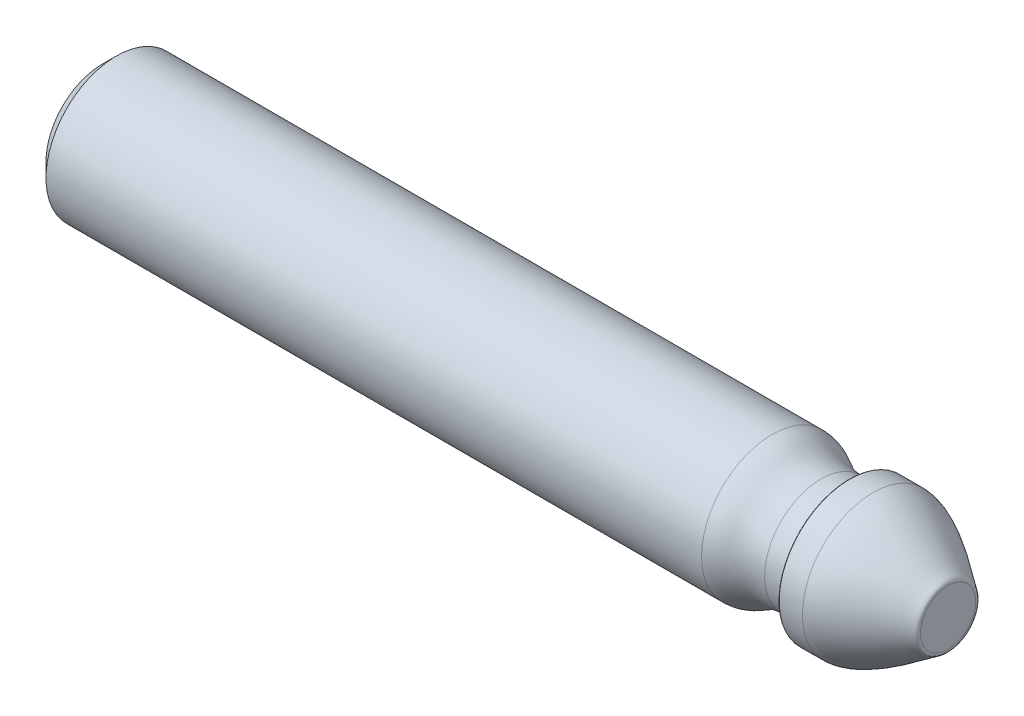
SolidWorks part; units mm, degrees
material "Alloy Steel"
ref_plane "Front" through (0, 0, 0) normal (0, 0, 1) x (1, 0, 0)
ref_plane "Top" through (0, 0, 0) normal (0, 1, 0) x (1, 0, 0)
ref_plane "Right" through (0, 0, 0) normal (1, 0, 0) x (0, 0, -1)
sketch "Sketch1" plane through (0, 0, 0) normal (0, 0, 1) x (1, 0, 0)
  line L0 (-19.05, 0) -> (19.05, 0) construction
  line L1 (19.05, 3.175) -> (19.05, -3.175) construction
  line L2 (-19.05, 3.175) -> (-19.05, -3.175) construction
  dimension "Length" = 38.1
  dimension "Diameter" = 6.35
sketch "Sketch2" plane through (0, 0, 0) normal (1, 0, 0) x (0, 0, -1)
  circle A0 centre (0, 0) radius 3.175
extrude "Extrude1" add sketch "Sketch2" against normal up to vertex (19.05 mm away) and the other way up to vertex (19.05 mm away) up to point (-19.05, 3.175, 0) other way up to point (19.05, 3.175, 0)
chamfer "Chamfer1" distance 0.635 angle 45 2 edges at (19.05, 0, -3.175) (-19.05, 0, -3.175)
sketch "Sketch3" plane through (0, 0, 0) normal (0, 0, 1) x (1, 0, 0)
  line L0 (-19.05, 0) -> (19.05, 0) construction
  line L1 (-19.05, 2.54) -> (-19.05, -2.54) construction
  line L2 (19.05, -2.54) -> (19.05, 2.54) construction
  line L3 (18.415, 3.175) -> (-18.415, 3.175) construction
  line L4 (15.6622, 3.175) -> (14.5934, 3.175)
  line L5 (16.629, 3.175) -> (14.655, 3.175) construction
  line L6 (19.05, 0.802) -> (19.05, 1.6965) construction
  line L7 (19.05, 1.2434) -> (19.05, 3.175)
  line L8 (19.05, 3.175) -> (15.6622, 3.175)
  line L9 (14.5934, 3.175) -> (14.5934, 2.54)
  line L10 (14.5934, 2.54) -> (13.3234, 2.54)
  line L11 (11.1187, 3.175) -> (14.5934, 3.175)
  line L12 (11.6265, 3.175) -> (9.464, 3.175) construction
  line L13 (14.3233, 2.54) -> (12.3233, 2.54) construction
  line L14 (11.1187, 3.175) -> (14.5934, 3.175)
  spline S0 degree 3 poles (15.6622, 3.175) (16.6428, 3.175) (18.614, 1.6311) (19.0441, 1.3825) (19.05, 1.3487) (19.05, 1.2434) knots 0 0 0 0 0.565725 0.665725 1 1 1 1
  spline S1 degree 3 poles (11.1187, 3.175) (11.9879, 3.175) (12.0734, 2.54) (13.3234, 2.54) knots 0 0 0 0 1 1 1 1
revolve "Cut-Revolve1" cut sketch "Sketch3" angle 360 about L0 region at (13.3125, 2.889, 0) region at (18.092, 2.592, 0)
fillet "Fillet1" radius 0.0254 1 edges at (14.5934, 0, 3.175)
equation "\"D1@Chamfer1\" = \"Diameter@Sketch1\"*.1"
